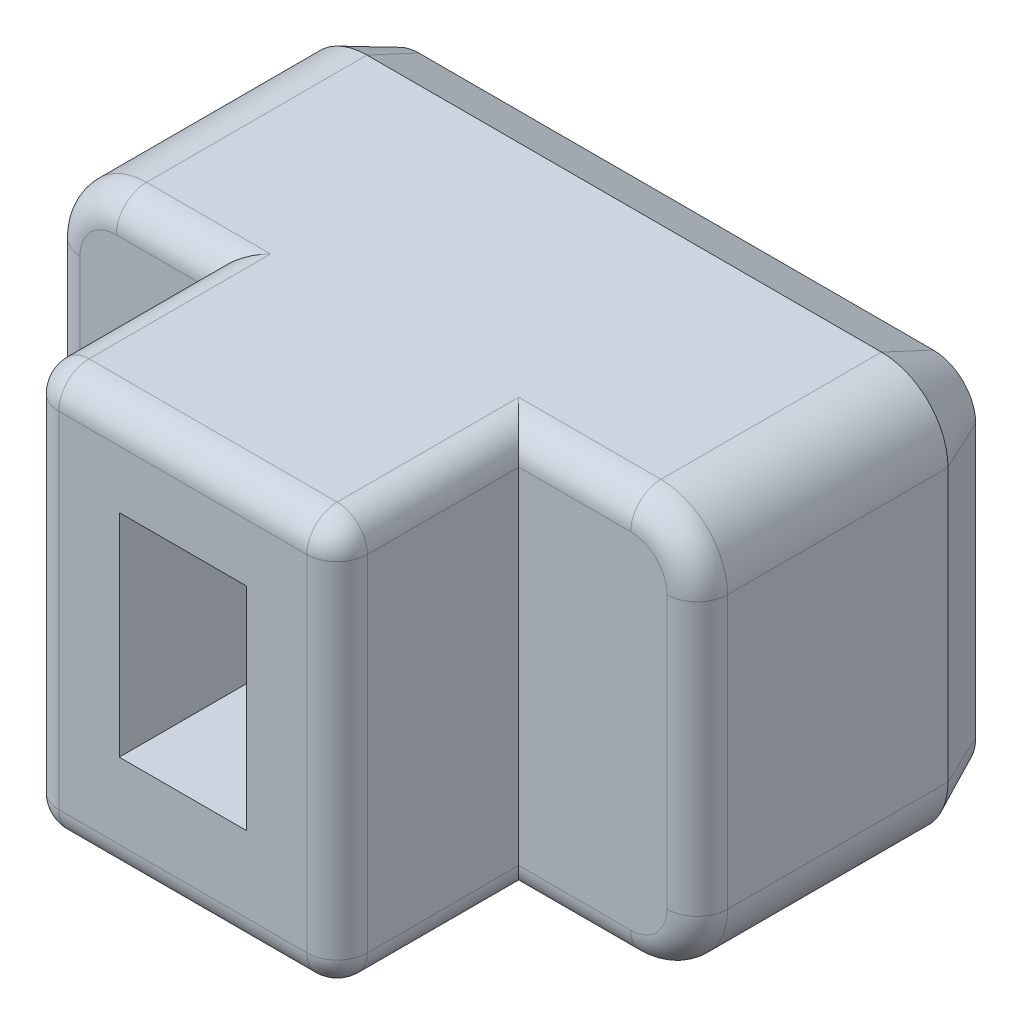
SolidWorks part; units mm, degrees
ref_plane "Plan de face" through (0, 0, 0) normal (0, 0, 1) x (1, 0, 0)
ref_plane "Plan de dessus" through (0, 0, 0) normal (0, 1, 0) x (1, 0, 0)
ref_plane "Plan de droite" through (0, 0, 0) normal (1, 0, 0) x (0, 0, -1)
sketch "Esquisse2" plane through (0, 0, 0) normal (0, 0, 1) x (1, 0, 0)
  line L1 (1.1, 0) -> (9.6, 0)
  line L2 (0, 1.1) -> (0, 5.6)
  line L3 (1.1, 6.7) -> (9.6, 6.7)
  line L4 (10.7, 1.1) -> (10.7, 5.6)
  arc A0 (9.6, 6.7) -> (10.7, 5.6) centre (9.6, 5.6) cw
  arc A1 (9.6, 0) -> (10.7, 1.1) centre (9.6, 1.1) ccw
  arc A2 (1.1, 0) -> (0, 1.1) centre (1.1, 1.1) cw
  arc A3 (0, 5.6) -> (1.1, 6.7) centre (1.1, 5.6) cw
  point P7 (10.7, 6.7)
  point P12 (0, 0)
  point P15 (0, 6.7)
  dimension "D3" = 1.1
  dimension "D1" = 10.7
  dimension "D2" = 6.7
extrude "Boss.-Extru.1" add sketch "Esquisse2" along normal blind 8
sketch "Esquisse3" plane through (0, 0, 8) normal (0, 0, 1) x (1, 0, 0)
  line L0 (0, 5.6) -> (0, 1.1) construction
  line L1 (4.15, 5.25) -> (6.25, 5.25)
  line L2 (4.15, 5.25) -> (4.15, 1.75)
  line L3 (4.15, 1.75) -> (6.25, 1.75)
  line L4 (6.25, 5.25) -> (6.25, 1.75)
  line L5 (10.7, 1.1) -> (10.7, 5.6) construction
  line L6 (9.6, 6.7) -> (1.1, 6.7) construction
  line L7 (1.1, 0) -> (9.6, 0) construction
  dimension "D1" = 2.1
  dimension "D2" = 3.5
  dimension "D3" = 4.15
  dimension "D4" = 4.45
  dimension "D5" = 1.45
  dimension "D6" = 1.75
extrude "Enlèv. mat.-Extru.1" cut sketch "Esquisse3" against normal blind 3
sketch "Esquisse4" plane through (0, 0, 8) normal (0, 0, 1) x (1, 0, 0)
  line L0 (2.65, 6.7) -> (2.65, 0)
  line L1 (9.6, 6.7) -> (1.1, 6.7) construction
  line L2 (1.1, 0) -> (9.6, 0) construction
  line L3 (2.65, 0) -> (7.75, 0)
  line L4 (7.75, 0) -> (7.75, 6.7)
  line L5 (7.75, 6.7) -> (2.65, 6.7)
  line L6 (4.15, 5.25) -> (4.15, 1.75) construction
  line L7 (6.25, 1.75) -> (6.25, 5.25) construction
  dimension "D1" = 1.5
  dimension "D2" = 1.5
extrude "Enlèv. mat.-Extru.2" cut sketch "Esquisse4" against normal blind 3 flip side to cut
fillet "Congé1" radius 0.5 18 edges at (8.675, 0, 5) (10.3778, 0.3222, 5) (10.7, 3.35, 5) (10.3778, 6.3778, 5) (1.875, 6.7, 5) (0.3222, 6.3778, 5) (1.875, 0, 5) (0.3222, 0.3222, 5) (7.75, 6.7, 6.5) (2.65, 6.7, 6.5) (7.75, 0, 6.5) (2.65, 0, 6.5) (2.65, 3.35, 8) (5.2, 6.7, 8) (7.75, 3.35, 8) (5.2, 0, 8) (8.675, 6.7, 5) (0, 3.35, 5)
chamfer "Chanfrein1" distance 0.4 angle 65 8 edges at (5.35, 0, 0) (10.3778, 0.3222, 0) (0.3222, 0.3222, 0) (10.7, 3.35, 0) (0, 3.35, 0) (10.3778, 6.3778, 0) (0.3222, 6.3778, 0) (5.35, 6.7, 0) first distance on face at (5.35, 3.35, 0)
ref_plane "Plan1" through (0, 0, 0.2) normal (0, 0, 1) x (1, 0, 0)
sketch "Esquisse5" plane through (0, 0, 0.2) normal (0, 0, 1) x (1, 0, 0)
  line L0 (-0.9378, 5.3566) -> (11.6517, 5.3566) construction
  text T0 "VS-" font "Century Gothic" height 4
extrude "Enlèv. mat.-Extru.3" cut sketch "Esquisse5" against normal blind 0.3
extrude "Boss.-Extru.2" add sketch "Esquisse5<3>" against normal blind 0.2 from offset 0.2 offset against normal yes
sketch "Esquisse5<3>" plane through (0, 0, 0.2) normal (0, 0, 1) x (1, 0, 0) same geometry as "Esquisse5"
